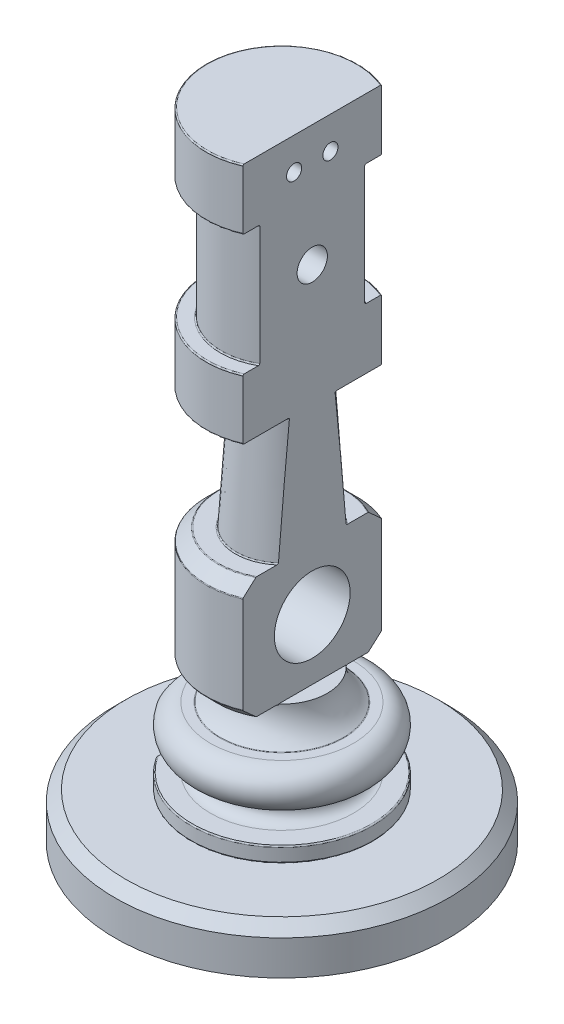
SolidWorks part; units mm, degrees
material "AISI 1020"
ref_plane "Front Plane" through (0, 0, 0) normal (0, 0, 1) x (1, 0, 0)
ref_plane "Top Plane" through (0, 0, 0) normal (0, 1, 0) x (1, 0, 0)
ref_plane "Right Plane" through (0, 0, 0) normal (1, 0, 0) x (0, 0, -1)
sketch "Sketch1" plane through (0, 0, 0) normal (1, 0, 0) x (0, 0, -1)
  line L0 (0, 26.7524) -> (0, -39.9226) construction
  line L1 (0, 26.7524) -> (-7.9375, 26.7524)
  line L2 (-7.9375, 26.7524) -> (-7.9375, 20.4024)
  line L3 (-7.9375, 20.4024) -> (-6.35, 20.4024)
  line L4 (-6.35, 20.4024) -> (-6.35, 7.7024)
  line L5 (-6.35, 7.7024) -> (-7.9375, 7.7024)
  line L6 (-7.9375, 7.7024) -> (-7.9375, 1.3524)
  line L7 (-7.9375, 1.3524) -> (-3.9687, 1.3524)
  line L8 (-3.9687, 1.3524) -> (-4.7625, -11.3476)
  line L9 (-4.7625, -11.3476) -> (-7.9375, -11.3476)
  line L10 (-7.9375, -11.3476) -> (-7.9375, -24.0476)
  line L11 (-7.9375, -24.0476) -> (-4.7625, -24.0476)
  line L12 (-6.477, -27.2295) -> (-7.493, -27.2295)
  line L13 (-7.493, -33.5726) -> (-9.525, -33.5726)
  line L14 (-9.525, -33.5726) -> (-9.525, -35.1601)
  line L15 (-9.525, -35.1601) -> (-4.7625, -35.1601)
  line L16 (-4.7625, -35.1601) -> (-4.7625, -39.9226)
  line L17 (-4.7625, -39.9226) -> (0, -39.9226)
  line L18 (0, 26.7524) -> (0, -39.9226)
  arc A0 (-4.7625, -24.0476) -> (-6.477, -27.2295) centre (-8.5725, -24.0476) cw
  arc A1 (-7.493, -27.2295) -> (-7.493, -31.2935) centre (-7.493, -29.2615) ccw
  arc A2 (-7.493, -31.2935) -> (-7.493, -33.5726) centre (-7.493, -32.4331) cw
  point P12 (-5.9531, 1.3524)
  point P28 (-6.35, -11.3476)
  dimension "D15" = 19.05
  dimension "D18" = 3.81
  dimension "D1" = 66.675
  dimension "D2" = 15.875
  dimension "D3" = 12.7
  dimension "D4" = 15.875
  dimension "D5" = 7.9375
  dimension "D6" = 9.525
  dimension "D7" = 12.7
  dimension "D8" = 6.35
  dimension "D9" = 6.35
  dimension "D10" = 25.4
  dimension "D11" = 12.7
  dimension "D12" = 15.875
  dimension "D13" = 9.525
  dimension "D14" = 12.954
  dimension "D16" = 14.986
  dimension "D17" = 19.05
  dimension "D19" = 11.1125
  dimension "D20" = 1.5875
  dimension "D21" = 9.525
revolve "Revolve1" add sketch "Sketch1" angle 360 about L0
sketch "Sketch2" plane through (0, 0, 0) normal (1, 0, 0) x (0, 0, -1)
  line L0 (0, -39.9226) -> (0, -35.1601) construction
  line L1 (-4.7625, -39.9226) -> (4.7625, -39.9226) construction
  line L2 (-4.7625, -35.1601) -> (4.7625, -35.1601) construction
  line L3 (-4.7625, -39.9226) -> (-17.4625, -39.9226)
  line L4 (-17.4625, -39.9226) -> (-17.4625, -36.2826)
  line L7 (-4.7625, -35.1601) -> (-4.7625, -39.9226)
  line L8 (-17.4625, -36.2826) -> (-16.34, -35.1601)
  line L9 (-16.34, -35.1601) -> (-4.7625, -35.1601)
  dimension "D1" = 34.925
  dimension "D2" = 45
  dimension "D3" = 1.5875
revolve "Revolve2" add sketch "Sketch2" angle 360 about L0
sketch "Sketch3" plane through (0, 26.7524, 0) normal (0, 1, 0) x (1, 0, 0)
  line L1 (3.175, 12.7) -> (15.875, 12.7)
  line L2 (3.175, 12.7) -> (3.175, -12.7)
  line L3 (3.175, -12.7) -> (15.875, -12.7)
  line L4 (15.875, 12.7) -> (15.875, -12.7)
  line L5 (3.175, 12.7) -> (15.875, -12.7) construction
  line L6 (3.175, -12.7) -> (15.875, 12.7) construction
  circle A1 centre (0, 0) radius 9.525 construction
  point P0 (9.525, 0)
  dimension "D1" = 12.7
  dimension "D2" = 12.7
  dimension "D3" = 25.4
chamfer "Chamfer1" distance 1.27 angle 45 2 edges at (0, -11.3476, 7.9375) (0, -24.0476, 7.9375)
extrude "Cut-Extrude1" cut sketch "Sketch3" against normal up to surface (50.8 mm away) contours L4 L3 L2 L1 up to face at (0, -24.0476, -6.6675)
sketch "Sketch4" plane through (3.175, 0, 0) normal (1, 0, 0) x (0, 0, -1)
  line L0 (-3.5498, -11.3476) -> (-5.863, -11.3476) construction
  line L1 (-7.2748, 20.4024) -> (-5.4993, 20.4024) construction
  circle A0 centre (0, -17.6976) radius 3.9688
  circle A1 centre (0, 14.0524) radius 1.5875
  dimension "D1" = 7.9375
  dimension "D3" = 3.175
  dimension "D2" = 6.35
  dimension "D4" = 6.35
extrude "Cut-Extrude2" cut sketch "Sketch4" against normal through all
sketch "Sketch5" plane through (3.175, 0, 0) normal (1, 0, 0) x (0, 0, -1)
  circle A0 centre (0, 14.0524) radius 3.175
  dimension "D1" = 6.35
extrude "Cut-Extrude4" cut sketch "Sketch5" against normal through all from offset 6.35 contours A0 offset against normal yes
sketch "Sketch6" plane through (0, -35.1601, 0) normal (0, 1, 0) x (1, 0, 0)
  line L1 (-20.6375, 10.3146) -> (-7.9375, 10.3146)
  line L2 (-20.6375, 10.3146) -> (-20.6375, -15.0854)
  line L3 (-20.6375, -15.0854) -> (-7.9375, -15.0854)
  line L4 (-7.9375, 10.3146) -> (-7.9375, -15.0854)
  line L5 (-20.6375, 10.3146) -> (-7.9375, -15.0854) construction
  line L6 (-20.6375, -15.0854) -> (-7.9375, 10.3146) construction
  circle A1 centre (0, 0) radius 9.525 construction
  point P0 (-14.2875, -2.3854)
  dimension "D1" = 25.4
  dimension "D2" = 12.7
  dimension "D3" = 17.4625
extrude "Cut-Extrude5" cut sketch "Sketch6" along normal up to surface (11.1125 mm away) contours L2 L3 L4 L1 up to face at (-1.27, -24.0476, 0)
sketch "Sketch8" plane through (3.175, 0, 0) normal (1, 0, 0) x (0, 0, -1)
  line L0 (0, 26.7524) -> (0, 23.3844) construction
  line L1 (7.2748, 26.7524) -> (-7.2748, 26.7524) construction
  line L2 (0, 23.3844) -> (-1.9037, 23.3844) construction
  circle A0 centre (-1.9037, 23.3844) radius 0.7937
  circle A1 centre (1.9037, 23.3844) radius 0.7937
  dimension "D3" = 1.5875
  dimension "D1" = 3.368
  dimension "D2" = 3.8075
extrude "Cut-Extrude7" cut sketch "Sketch8" against normal through all contours A0
extrude "Cut-Extrude8" cut sketch "Sketch8<3>" against normal blind 7.9375 contours A1
sketch "Sketch8<3>" plane through (3.175, 0, 0) normal (1, 0, 0) x (0, 0, -1) same geometry as "Sketch8"
fillet "Fillet1" radius 0.127 16 edges at (-4.7625, -11.3476, 0) (-6.6675, -11.3476, 0) (-7.9375, -12.6176, 0) (0, -27.2295, 6.477) (9.525, -35.1601, 0) (9.525, -33.5726, 0) (-4.7625, -24.0476, 0) (-6.6675, -24.0476, 0) (-7.9375, -22.7776, 0) (-3.9688, 1.3524, 0) (-7.9375, 1.3524, 0) (-7.9375, 7.7024, 0) (-6.35, 7.7024, 0) (-6.35, 20.4024, 0) (-7.9375, 20.4024, 0) (-7.9375, 26.7524, 0)
